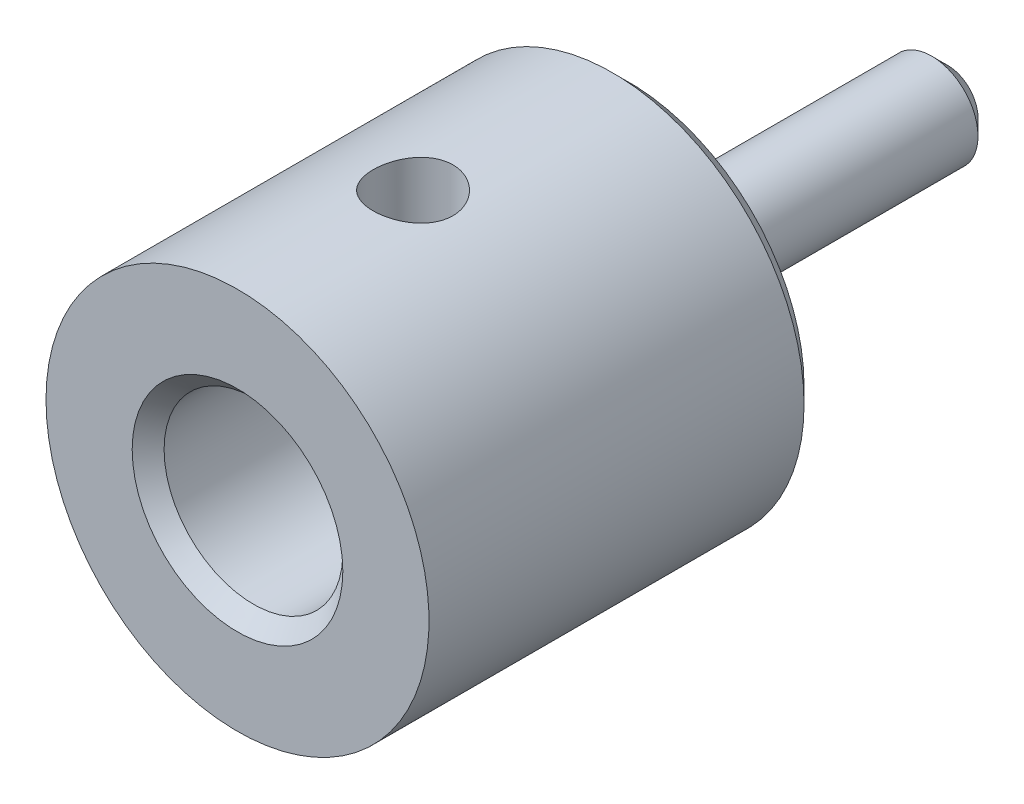
SolidWorks part; units mm, degrees
material "Alliage 1060"
ref_plane "Plan de face" through (0, 0, 0) normal (0, 0, 1) x (1, 0, 0)
ref_plane "Plan de dessus" through (0, 0, 0) normal (0, 1, 0) x (1, 0, 0)
ref_plane "Plan de droite" through (0, 0, 0) normal (1, 0, 0) x (0, 0, -1)
sketch "Esquisse1" plane through (0, 0, 0) normal (0, 1, 0) x (1, 0, 0)
  line L0 (0, 0) -> (6, 0)
  line L1 (6, 0) -> (6, 12.25)
  line L2 (6, 12.25) -> (1.45, 12.25)
  line L3 (1.45, 12.25) -> (1.45, 22.25)
  line L4 (1.45, 22.25) -> (0, 22.25)
  line L5 (0, 22.25) -> (0, 0)
  dimension "D1" = 6
  dimension "D2" = 12.25
  dimension "D3" = 1.45
  dimension "D4" = 10
revolve "Révolution1" add sketch "Esquisse1" angle 360 about L5
sketch "Esquisse2" plane through (0, 0, 0) normal (0, 0, 1) x (1, 0, 0)
  circle A0 centre (0, 0) radius 2.8
  dimension "D1" = 5.6
extrude "Enlèv. mat.-Extru.1" cut sketch "Esquisse2" against normal blind 3
sketch "Esquisse3" plane through (0, 0, -3) normal (0, 0, 1) x (1, 0, 0)
  line L0 (-1.852, 2.1) -> (1.852, 2.1)
  line L1 (0, 0) -> (0, 2.1) construction
  arc A1 (-1.852, 2.1) -> (1.852, 2.1) centre (0, 0) ccw
  circle A2 centre (0, 0) radius 2.8 construction
  dimension "D1" = 2.1
extrude "Enlèv. mat.-Extru.2" cut sketch "Esquisse3" against normal blind 5.5
sketch "Esquisse9" plane through (0, 0, 0) normal (0, 1, 0) x (1, 0, 0)
  line L0 (0, 5.5) -> (0, 0) construction
  circle A0 centre (0, 5.5) radius 2.5
  dimension "D2" = 5
  dimension "D1" = 5.5
ref_plane "Plan1" through (0, 6, 0) normal (0, 1, 0) x (1, 0, 0)
sketch "Esquisse12" plane through (0, 6, 0) normal (0, 1, 0) x (1, 0, 0)
  point P0 (0, 5.5)
chamfer "Chanfrein1" distance 0.5 angle 45 3 edges at (2.8, 0, 0) (-1.45, 0, -22.25) (-6, 0, -12.25)
sketch "Esquisse16" plane through (0, 0, 0) normal (0, 1, 0) x (1, 0, 0)
  line L0 (1.45, 12.25) -> (1.45, 21.75) construction
  line L1 (1.45, 12.75) -> (-1.45, 12.75)
  line L2 (1.45, 12.75) -> (1.45, 22.25)
  line L3 (1.45, 22.25) -> (-1.45, 22.25)
  line L4 (-1.45, 12.75) -> (-1.45, 22.25)
  line L5 (-1.45, 21.75) -> (-1.45, 12.25) construction
  line L6 (0.95, 22.25) -> (-0.95, 22.25) construction
  line L7 (5.5, 12.25) -> (-5.5, 12.25) construction
  dimension "D1" = 0.5
extrude "Enlèv. mat.-Extru.5" [suppressed] cut sketch "Esquisse16" along normal up to next from offset 1.1
hole_wizard "Trou pour taraudage pour trou taraudé M32" positions "Esquisse18" profile "Esquisse19" hole size "M3" standard "ISO"
sketch "Esquisse18" plane through (0, 6, 0) normal (0, 1, 0) x (1, 0, 0)
  point P0 (0, 5.5)
sketch "Esquisse19" plane through (0, 6, -5.5) normal (1, 0, 0) x (0, 0, 1)
  line L0 (0, 0) -> (0, 6.7511)
  line L1 (0, 6.7511) -> (1.25, 6)
  line L2 (1.25, 6) -> (1.25, 0)
  line L5 (1.25, 0) -> (0, 0)
  line L10 (0, 6.7511) -> (-1.25, 6) construction
  line L11 (0, -6.35) -> (0, 107.95) construction
  dimension "Diamètre du perçage" = 2.5
  dimension "Profondeur du perçage" = 6
  dimension "Angle de pointe" = 118
